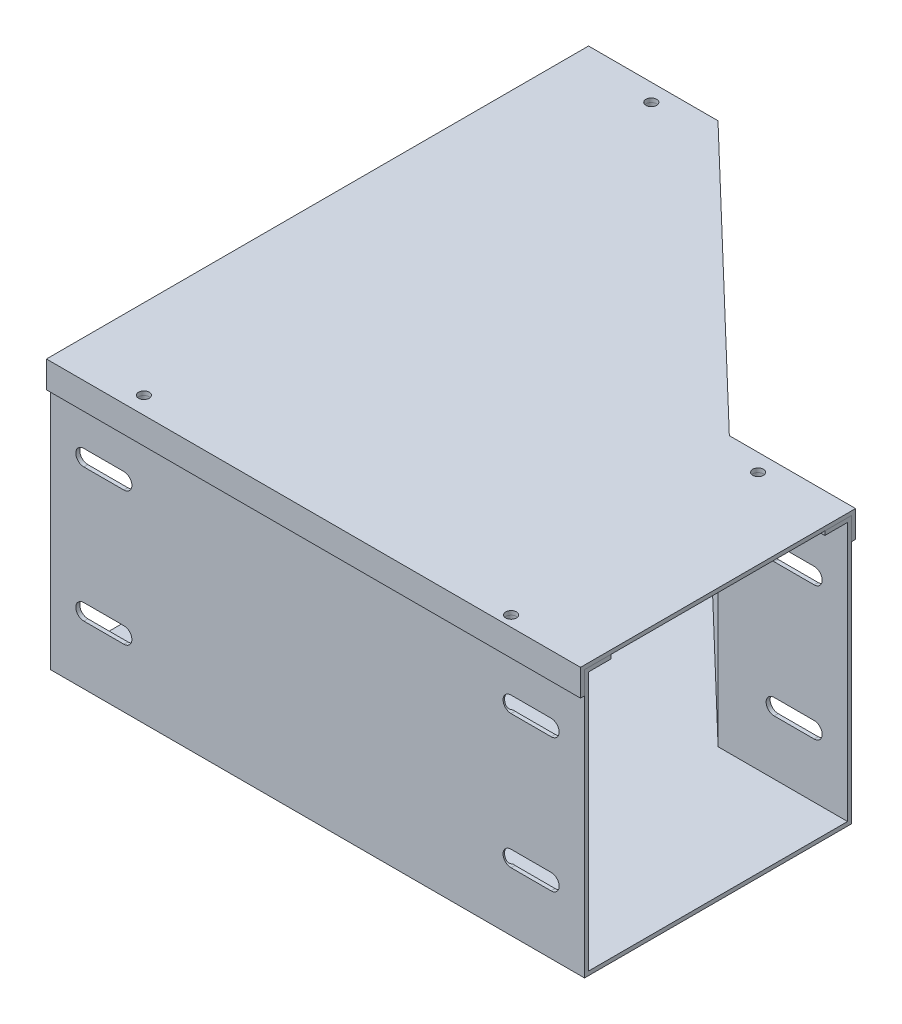
SolidWorks part; units mm, degrees
material "Plain Carbon Steel"
ref_plane "Front Plane" through (0, 0, 0) normal (0, 0, 1) x (1, 0, 0)
ref_plane "Top Plane" through (0, 0, 0) normal (0, 1, 0) x (1, 0, 0)
ref_plane "Right Plane" through (0, 0, 0) normal (1, 0, 0) x (0, 0, -1)
ref_plane "Plane1" through (0, -50, 0) normal (0, 1, 0) x (1, 0, 0)
sketch "Sketch1" plane through (0, -50, 0) normal (0, 1, 0) x (1, 0, 0)
  line L2 (100, 50) -> (100, -50)
  line L3 (-100, 150) -> (-100, -50)
  line L5 (100, -50) -> (52.1237, -50)
  line L8 (-100, 150) -> (-52.1237, 150)
  line L9 (-100, -50) -> (-52.1237, -50)
  line L11 (100, 50) -> (52.1237, 50)
  line L12 (0, -50) -> (0, 100) construction
  line L13 (-100, 0) -> (100, 0) construction
  line L14 (52.1237, -50) -> (-52.1237, -50)
  line L15 (52.1237, 50) -> (-52.1237, 150)
  dimension "Width2" = 100
  dimension "Length" = 200
  dimension "Width1" = 200
  dimension "LeftRightReducer" = 50
extrude "Boss-Extrude1" add sketch "Sketch1" along normal blind 1.5
sketch "Sketch2" plane through (0, -50, 0) normal (0, -1, 0) x (-1, 0, 0)
  line L10 (52.1237, 150) -> (-52.1237, 50)
  line L11 (100, 150) -> (52.1237, 150)
  line L12 (100, -50) -> (100, 150)
  line L13 (52.1237, -50) -> (100, -50)
  line L14 (-52.1237, -50) -> (52.1237, -50)
  line L15 (-100, -50) -> (-52.1237, -50)
  line L16 (-100, 50) -> (-100, -50)
  line L17 (-52.1237, 50) -> (-100, 50)
  line L18 (52.1237, 150) -> (-52.1237, 50)
  line L19 (100, 150) -> (52.1237, 150)
  line L21 (52.1237, -50) -> (100, -50)
  line L22 (-52.1237, -50) -> (52.1237, -50)
  line L23 (-100, -50) -> (-52.1237, -50)
  line L25 (-52.1237, 50) -> (-100, 50)
  dimension "D1" = 0
extrude "Extrude-Thin1" add sketch "Sketch2" against normal blind 100 thin thin type one direction reverse wall 1.5
sketch "Sketch3" plane through (0, 0, 0) normal (0, 0, 1) x (1, 0, 0)
  line L0 (72.5, 25) -> (87.5, 25) construction
  line L1 (72.5, 28) -> (87.5, 28)
  line L2 (72.5, 22) -> (87.5, 22)
  line L3 (72.5, -25) -> (87.5, -25) construction
  line L4 (72.5, -22) -> (87.5, -22)
  line L5 (72.5, -28) -> (87.5, -28)
  line L6 (60, 0) -> (100, 0) construction
  line L8 (-87.5, 25) -> (-72.5, 25) construction
  line L9 (80, -50) -> (80, 0) construction
  line L10 (-87.5, 28) -> (-72.5, 28)
  line L11 (80, 0) -> (80, 50) construction
  line L12 (-87.5, 22) -> (-72.5, 22)
  line L13 (-87.5, -25) -> (-72.5, -25) construction
  line L14 (-87.5, -22) -> (-72.5, -22)
  line L15 (-87.5, -28) -> (-72.5, -28)
  line L16 (-100, 0) -> (-60, 0) construction
  line L17 (-80, -50) -> (-80, 0) construction
  line L18 (-80, 0) -> (-80, 50) construction
  arc A0 (72.5, 28) -> (72.5, 22) centre (72.5, 25) ccw
  arc A1 (87.5, 22) -> (87.5, 28) centre (87.5, 25) ccw
  arc A2 (72.5, -22) -> (72.5, -28) centre (72.5, -25) ccw
  arc A3 (87.5, -28) -> (87.5, -22) centre (87.5, -25) ccw
  arc A4 (-87.5, 28) -> (-87.5, 22) centre (-87.5, 25) ccw
  arc A5 (-72.5, 22) -> (-72.5, 28) centre (-72.5, 25) ccw
  arc A6 (-87.5, -22) -> (-87.5, -28) centre (-87.5, -25) ccw
  arc A7 (-72.5, -28) -> (-72.5, -22) centre (-72.5, -25) ccw
  point P2 (80, 25)
  point P8 (80, -25)
  point P22 (-80, 25)
  point P30 (-80, -25)
  dimension "D1" = 3
  dimension "D6" = 3
  dimension "D2" = 15
  dimension "D3" = 50
  dimension "D4" = 40
  dimension "D5" = 100
  dimension "D7" = 100
extrude "Cut-Extrude1" cut sketch "Sketch3" against normal through all and the other way through all
ref_plane "Plane2" through (0, 50, 0) normal (0, 1, 0) x (1, 0, 0)
sketch "Sketch4" plane through (0, 50, 0) normal (0, 1, 0) x (1, 0, 0)
  line L14 (52.1237, 50) -> (-52.1237, 150)
  line L15 (-52.1237, 150) -> (-100, 150)
  line L16 (-100, 150) -> (-100, -50)
  line L17 (-100, -50) -> (-52.1237, -50)
  line L18 (-52.1237, -50) -> (52.1237, -50)
  line L19 (52.1237, -50) -> (100, -50)
  line L20 (100, -50) -> (100, 50)
  line L21 (100, 50) -> (52.1237, 50)
  line L22 (52.1237, 50) -> (-52.1237, 150)
  line L23 (-52.1237, 150) -> (-100, 150)
  line L25 (-100, -50) -> (-52.1237, -50)
  line L26 (-52.1237, -50) -> (52.1237, -50)
  line L27 (52.1237, -50) -> (100, -50)
  line L29 (100, 50) -> (52.1237, 50)
  dimension "D1" = 0
extrude "Extrude-Thin2" add sketch "Sketch4" against normal blind 1.5 thin thin type one direction reverse wall 10
sketch "Sketch5" plane through (0, 50, 0) normal (0, 1, 0) x (1, 0, 0)
  line L4 (100, -48.5) -> (100, 48.5) construction
  line L5 (-100, 148.5) -> (-100, -48.5) construction
  line L10 (52.1237, 50) -> (-52.1237, 150)
  line L11 (-52.1237, 150) -> (-100, 150)
  line L12 (-100, 150) -> (-100, -50)
  line L13 (-100, -50) -> (-52.1237, -50)
  line L14 (-52.1237, -50) -> (52.1237, -50)
  line L15 (52.1237, -50) -> (100, -50)
  line L16 (100, -50) -> (100, 50)
  line L17 (100, 50) -> (52.1237, 50)
  line L18 (52.1237, 50) -> (-52.1237, 150) construction
  line L19 (-52.1237, 150) -> (-100, 150) construction
  line L21 (-100, -50) -> (-52.1237, -50) construction
  line L22 (-52.1237, -50) -> (52.1237, -50) construction
  line L23 (52.1237, -50) -> (100, -50) construction
  line L25 (100, 50) -> (52.1237, 50) construction
  circle A0 centre (-70, 145) radius 2
  circle A1 centre (-70, -45) radius 2
  circle A2 centre (70, 45) radius 2
  circle A3 centre (70, -47.5) radius 2
  dimension "D1" = 30
  dimension "D3" = 4
  dimension "D2" = 30
  dimension "D4" = 0
  dimension "D5" = 5
  dimension "D6" = 5
  dimension "D7" = 5
  dimension "D8" = 5
extrude "Cut-Extrude2" cut sketch "Sketch5" against normal up to next
sketch "Sketch6" plane through (0, 50, 0) normal (0, 1, 0) x (1, 0, 0)
  line L8 (-52.1237, -50) -> (52.1237, -50)
  line L9 (-52.1237, 150) -> (-100, 150)
  line L10 (-100, 150) -> (-100, -50)
  line L11 (-100, -50) -> (-52.1237, -50)
  line L12 (-52.1237, -50) -> (52.1237, -50)
  line L13 (52.1237, -50) -> (100, -50)
  line L14 (100, -50) -> (100, 50)
  line L15 (100, 50) -> (52.1237, 50)
  line L16 (52.1237, 50) -> (-52.1237, 150)
  line L17 (-52.1237, 150) -> (-100, 150)
  line L18 (-100, 150) -> (-100, -50)
  line L19 (-100, -50) -> (-52.1237, -50)
  line L20 (52.1237, 50) -> (-52.1237, 150)
  line L21 (52.1237, -50) -> (100, -50)
  line L22 (100, -50) -> (100, 50)
  line L23 (100, 50) -> (52.1237, 50)
  dimension "D1" = 0
extrude "Boss-Extrude2" add sketch "Sketch6" along normal blind 1.5 separate body
sketch "Sketch7" plane through (0, 51.5, 0) normal (0, 1, 0) x (1, 0, 0)
  line L14 (52.1237, 50) -> (-52.1237, 150)
  line L15 (-52.1237, 150) -> (-100, 150)
  line L16 (-100, 150) -> (-100, -50)
  line L17 (-100, -50) -> (-52.1237, -50)
  line L18 (-52.1237, -50) -> (52.1237, -50)
  line L19 (52.1237, -50) -> (100, -50)
  line L20 (100, -50) -> (100, 50)
  line L21 (100, 50) -> (52.1237, 50)
  line L22 (52.1237, 50) -> (-52.1237, 150)
  line L23 (-52.1237, 150) -> (-100, 150)
  line L25 (-100, -50) -> (-52.1237, -50)
  line L26 (-52.1237, -50) -> (52.1237, -50)
  line L27 (52.1237, -50) -> (100, -50)
  line L29 (100, 50) -> (52.1237, 50)
  dimension "D1" = 0
extrude "Extrude-Thin3" add sketch "Sketch7" against normal blind 10 thin thin type one direction wall 1.5
sketch "Sketch8" plane through (0, 51.5, 0) normal (0, 1, 0) x (1, 0, 0)
  circle A1 centre (70, -47.5) radius 2
  circle A2 centre (70, -47.5) radius 2
  circle A3 centre (70, 45) radius 2
  circle A4 centre (70, 45) radius 2
  circle A5 centre (-70, -45) radius 2
  circle A6 centre (-70, -45) radius 2
  circle A7 centre (-70, 145) radius 2
  circle A8 centre (-70, 145) radius 2
  dimension "D1" = 0
  dimension "D2" = 0
  dimension "D3" = 0
  dimension "D4" = 0
extrude "Cut-Extrude3" cut sketch "Sketch8" against normal up to next (1.5 mm away)
sketch "Sketch9" plane through (0, 0, 0) normal (0, -1, 0) x (-1, 0, 0)
  line L0 (-100, 50) -> (-100, -50) construction
  line L1 (100, -50) -> (100, 150) construction
  point P0 (100, 50)
  point P1 (0, 0)
  point P2 (-100, 0)
other "CPoint1" parameters "Diameter"=10, "StubLength"=200
ref_axis "Axis2" through (-110, 0, -50) along (1, 0, 0)
other "CPoint2" parameters "Diameter"=10, "StubLength"=100
ref_axis "Axis1" through (110, 0, 0) along (-1, 0, 0)
equation "\"D5@Extrude-Thin1\"=\"Thickness@Boss-Extrude1\""
equation "\"D3@Sketch3\"=\"Height@Extrude-Thin1\"/2"
equation "\"D5@Sketch3\"=\"Length@Sketch1\"/2"
equation "\"D7@Sketch3\"=\"D5@Sketch3\""
equation "\"D1@Plane2\"=\"PlaneOffset@Plane1\""
